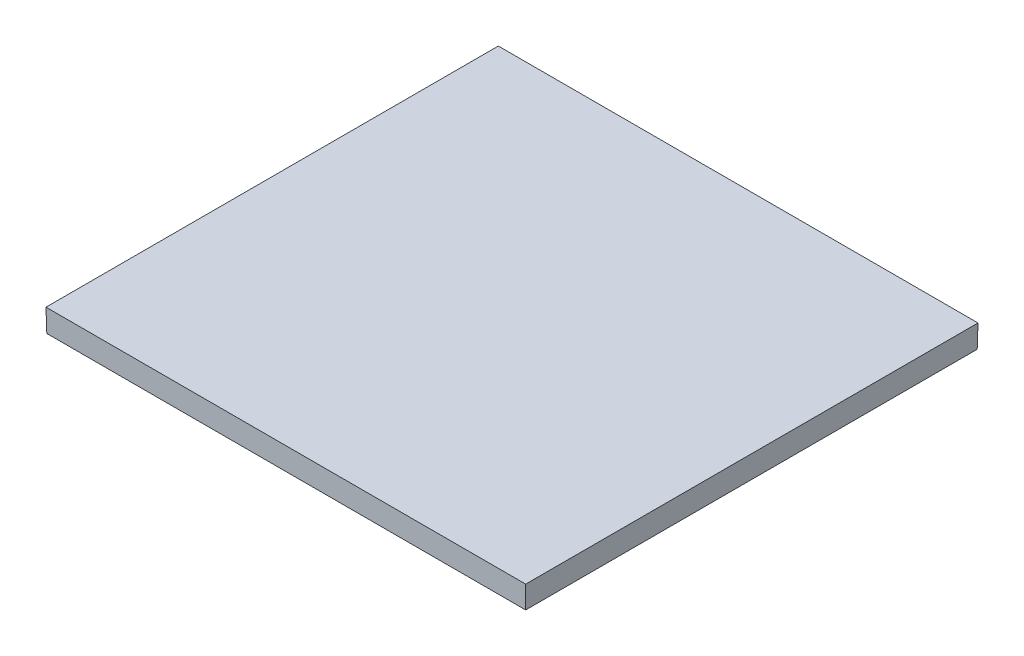
SolidWorks part; units mm, degrees
ref_plane "Front Plane" through (0, 0, 0) normal (0, 0, 1) x (1, 0, 0)
ref_plane "Top Plane" through (0, 0, 0) normal (0, 1, 0) x (1, 0, 0)
ref_plane "Right Plane" through (0, 0, 0) normal (1, 0, 0) x (0, 0, -1)
ref_axis "Axis1" through (-33.0333, 0, 0) along (1, 0, 0)
ref_axis "Axis2" through (0, 24.5224, 0) along (0, -1, 0)
ref_axis "Axis3" through (0, 0, -30.7663) along (0, 0, 1)
sketch "Sketch1" plane through (0, 0, 0) normal (0, 1, 0) x (1, 0, 0)
  line L1 (-105, -99) -> (105, -99)
  line L2 (-105, -99) -> (-105, 99)
  line L3 (-105, 99) -> (105, 99)
  line L4 (105, -99) -> (105, 99)
  line L5 (-105, -99) -> (105, 99) construction
  line L6 (-105, 99) -> (105, -99) construction
  point P0 (0, 0)
  dimension "D1" = 210
  dimension "D2" = 198
extrude "Boss-Extrude1" add sketch "Sketch1" along normal blind 10 draft 1 draft outward yes
